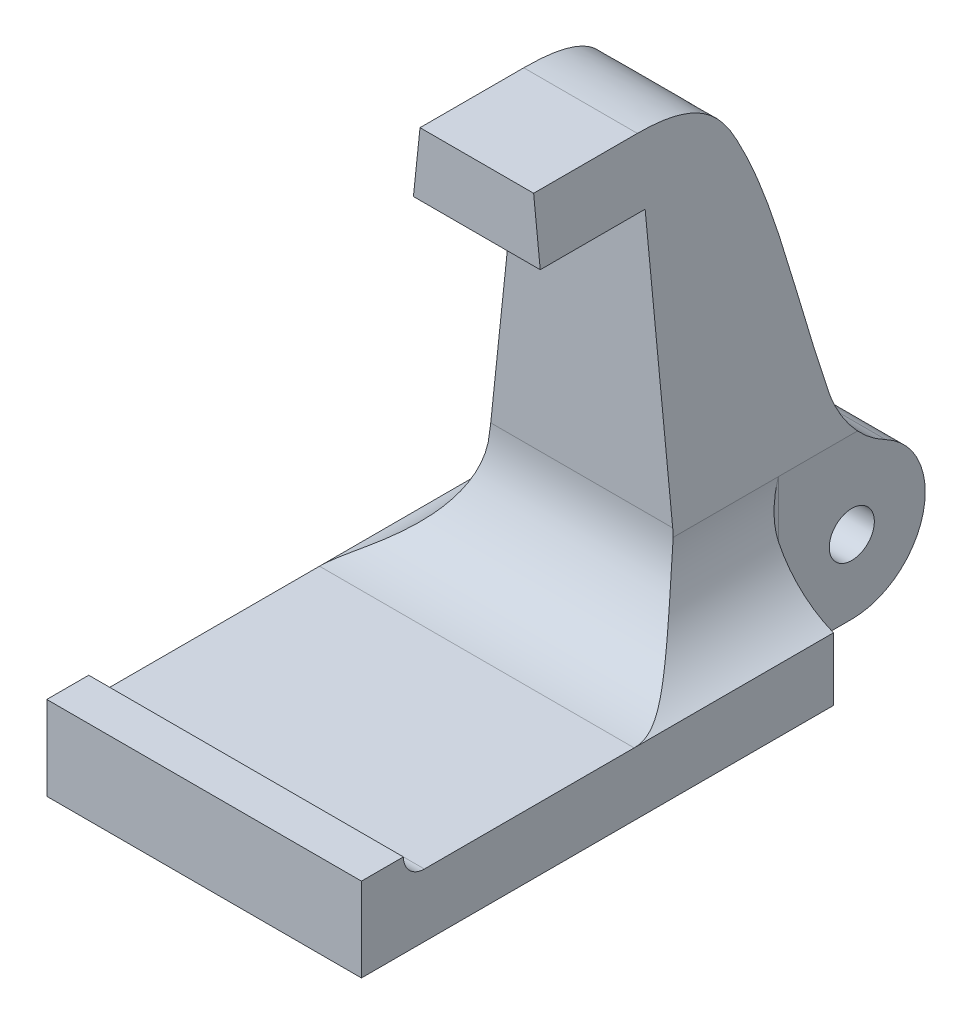
SolidWorks part; units mm, degrees
ref_plane "Front Plane" through (0, 0, 0) normal (0, 0, 1) x (1, 0, 0)
ref_plane "Top Plane" through (0, 0, 0) normal (0, 1, 0) x (1, 0, 0)
ref_plane "Right Plane" through (0, 0, 0) normal (1, 0, 0) x (0, 0, -1)
sketch "Sketch1" plane through (0, 0, 0) normal (0, 1, 0) x (1, 0, 0)
  line L0 (0, -64.9732) -> (0, 0) construction
  line L1 (-8.75, 0) -> (8.75, 0)
  line L2 (8.75, 0) -> (8.75, -15)
  line L3 (8.75, -15) -> (15, -15)
  line L4 (15, -15) -> (15, -60)
  line L5 (15, -60) -> (-15, -60)
  line L6 (-15, -15) -> (-15, -60)
  line L7 (-8.75, -15) -> (-15, -15)
  line L8 (-8.75, 0) -> (-8.75, -15)
  point P13 (0, -60)
  dimension "D1" = 30
  dimension "D2" = 45
  dimension "D3" = 15
  dimension "D4" = 17.5
extrude "Boss-Extrude1" add sketch "Sketch1" along normal blind 6
sketch "Sketch3" plane through (-8.75, 0, 0) normal (-1, 0, 0) x (0, 0, 1)
  line L10 (14, 6) -> (14, 7)
  line L11 (0, 7) -> (0, 6)
  line L12 (0, 0) -> (15, 0) construction
  line L13 (14, 6) -> (0, 6)
  line L14 (0, 6) -> (15, 6) construction
  arc A0 (14, 7) -> (0, 7) centre (7, 7) ccw
  dimension "D2" = 7
  dimension "D1" = 7
extrude "Boss-Extrude2" add sketch "Sketch3" against normal up to surface (17.5 mm away) up to face at (8.75, 3, 7.5)
sketch "Sketch5" plane through (-8.75, 0, 0) normal (-1, 0, 0) x (0, 0, 1)
  line L0 (7, 14) -> (7, 0) construction
  line L1 (0, 0) -> (15, 0) construction
  arc A0 (14, 7) -> (0, 7) centre (7, 7) ccw construction
  circle A1 centre (7, 7) radius 2.15
  dimension "D1" = 4.3
  dimension "D2" = 7
extrude "Cut-Extrude1" cut sketch "Sketch5" against normal up to surface (17.5 mm away) up to face at (8.75, 5.5, 9.6667)
fillet "Fillet1" radius 7 1 edges at (0, 0, 0)
sketch "Sketch6" plane through (0, 6, 0) normal (0, 1, 0) x (1, 0, 0)
  line L0 (0, -60) -> (0, 0) construction
  line L1 (-15, -60) -> (15, -60) construction
  line L2 (8.75, 0) -> (-8.75, 0) construction
  line L3 (2.25, -15) -> (-2.25, -15)
  line L4 (2.25, -15) -> (2.25, 0)
  line L5 (2.25, 0) -> (-2.25, 0)
  line L6 (-2.25, -15) -> (-2.25, 0)
  line L7 (2.25, -15) -> (-2.25, 0) construction
  line L8 (2.25, 0) -> (-2.25, -15) construction
  line L10 (8.75, -15) -> (-8.75, -15) construction
  point P5 (0, -7.5)
  dimension "D1" = 4.5
extrude "Cut-Extrude3" cut sketch "Sketch6" along normal blind 8 and the other way blind 8
sketch "Sketch7" plane through (8.75, 0, 0) normal (1, 0, 0) x (0, 0, -1)
  line L0 (-24, 6) -> (-24, 41)
  line L1 (-60, 6) -> (-15, 6) construction
  line L2 (-24, 41) -> (-34, 41)
  line L3 (-34, 41) -> (-34, 47)
  line L4 (-34, 47) -> (-24.1105, 47)
  line L6 (-14, 6) -> (-14, 7)
  line L8 (-24, 6) -> (-14, 6)
  line L10 (-19.2414, 47) -> (-2.1273, 47) construction
  arc A0 (-14, 7) -> (-7.1795, 13.9977) centre (-7, 7) cw
  circle A3 centre (-7, 7) radius 2.15 construction
  circle A4 centre (-7, 7) radius 2.15 construction
  arc A6 (0, 7) -> (-14, 7) centre (-7, 7) ccw construction
  spline S0 degree 3 poles (-24.1105, 47) (-17.8893, 47) (-11.6942, 37.8193) (-10.867, 25.4552) (-7.1795, 13.9977) knots 0 0 0 0 0.265029 1 1 1 1
  dimension "D5" = 0
  dimension "D1" = 10
  dimension "D2" = 35
  dimension "D3" = 6
  dimension "D4" = 10
extrude "Boss-Extrude3" add sketch "Sketch7" against normal up to surface (17.5 mm away) up to face at (-8.75, 7, 9.15)
sketch "Sketch8" plane through (-2.25, 0, 0) normal (1, 0, 0) x (0, 0, -1)
  line L3 (-15, 6) -> (-15, 7)
  line L5 (-7, 15) -> (-7, 7)
  line L6 (-15, 6) -> (-7, 6)
  line L7 (-7, 6) -> (-7, 7)
  arc A0 (-15, 7) -> (-7, 15) centre (-7, 7) cw
extrude "Cut-Extrude4" cut sketch "Sketch8" along normal up to surface (4.5 mm away) up to face at (2.25, 5.9213, 10.0967)
fillet "Fillet3" radius 10 3 edges at (0, 6, 24) (8.75, 6, 19.5) (-8.75, 6, 19.5)
fillet "Fillet6" radius 1 2 edges at (8.75, 7.6351, 15) (-8.75, 7.6351, 15)
fillet "Fillet7" radius 10 1 edges at (5.5, 13.9977, 7.1795)
ref_plane "Plane1" through (-10.2418, 1.0765, 0) normal (0.9945, -0.1045, 0) x (0, 0, 1)
sketch "Sketch9" plane through (-10.2418, 1.0765, 0) normal (0.9945, -0.1045, 0) x (0, 0, 1)
  line L1 (6.3535, -13.5188) -> (38.0706, -13.5188)
  line L2 (6.3535, -13.5188) -> (6.3535, -53.3281)
  line L3 (6.3535, -53.3281) -> (38.0706, -53.3281)
  line L4 (38.0706, -13.5188) -> (38.0706, -53.3281)
extrude "Cut-Extrude5" cut sketch "Sketch9" against normal blind 10
mirror "Mirror1" about plane through (0, 0, 0) normal (1, 0, 0) of "Cut-Extrude5"
sketch "Sketch10" plane through (15, 0, 0) normal (1, 0, 0) x (0, 0, -1)
  line L0 (-60, 6) -> (-60, 8)
  line L1 (-60, 8) -> (-56, 8)
  line L2 (-56, 8) -> (-56, 6)
  line L3 (-60, 6) -> (-34, 6) construction
  line L4 (-56, 6) -> (-60, 6)
  dimension "D1" = 4
  dimension "D2" = 2
extrude "Boss-Extrude4" add sketch "Sketch10" against normal up to surface (30 mm away) up to face at (-15, 3.6, 36.8)
fillet "Fillet8" radius 2 1 edges at (0, 6, 56)
